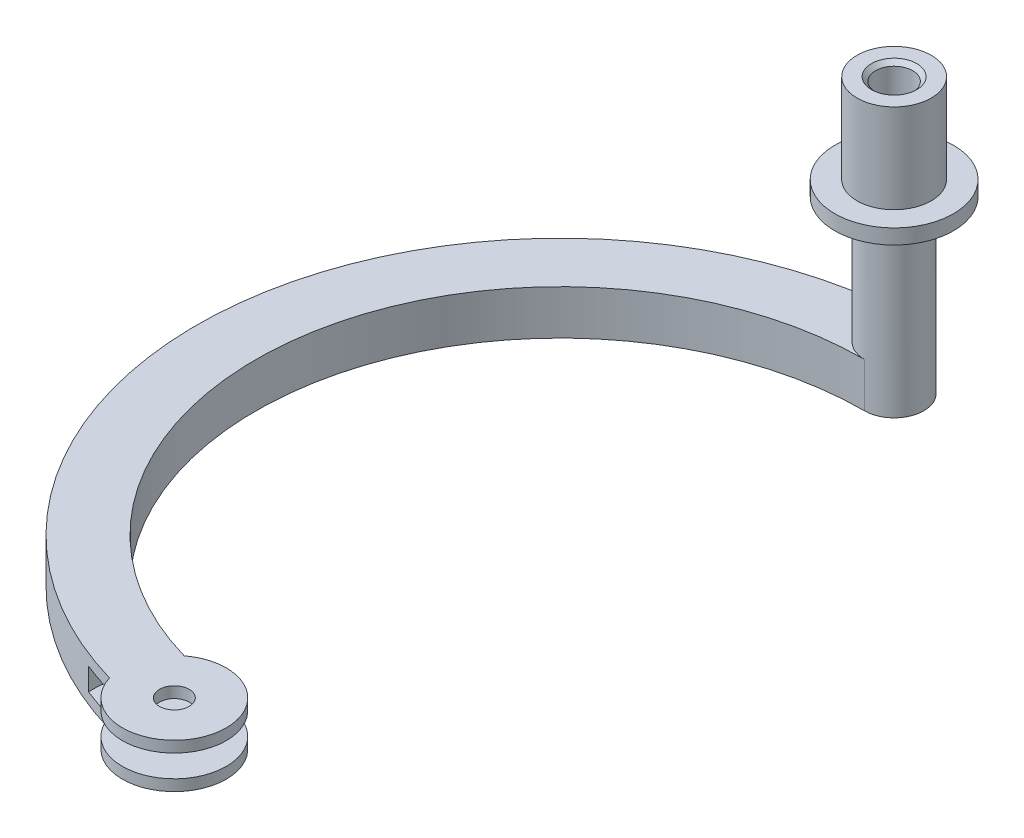
SolidWorks part; units mm, degrees
ref_plane "Front Plane" through (0, 0, 0) normal (0, 0, 1) x (1, 0, 0)
ref_plane "Top Plane" through (0, 0, 0) normal (0, 1, 0) x (1, 0, 0)
ref_plane "Right Plane" through (0, 0, 0) normal (1, 0, 0) x (0, 0, -1)
sketch "Sketch1" plane through (0, 0, 0) normal (0, 1, 0) x (1, 0, 0)
  circle A0 centre (0, 0) radius 2.5
  dimension "D1" = 5
extrude "Boss-Extrude1" add sketch "Sketch1" along normal blind 6
sketch "Sketch2" plane through (0, 0, 0) normal (0, -1, 0) x (1, 0, 0)
  circle A0 centre (0, 0) radius 4
  dimension "D1" = 8
extrude "Boss-Extrude2" add sketch "Sketch2" along normal blind 1
ref_plane "Plane1" through (0, -11, 0) normal (0, -1, 0) x (-1, 0, 0)
sketch "Sketch6" plane through (0, -11, 0) normal (0, -1, 0) x (-1, 0, 0)
  line L10 (0, 0) -> (0, -16.7806) construction
  arc A1 (6.8469, -46.0238) -> (5.6195, -42.2147) centre (3.5, -45) cw
  arc A2 (0, -2) -> (0, 2) centre (0, 0) cw
  arc A5 (0, 2) -> (6.8469, -46.0238) centre (0, -22.5) cw
  arc A6 (0, -2) -> (5.6195, -42.2147) centre (0, -22.5) cw
  dimension "D1" = 3.5
  dimension "D2" = 2
  dimension "D4" = 45
  dimension "D3" = 22.5
extrude "Boss-Extrude3" add sketch "Sketch6" along normal mid plane 3 separate body
sketch "Sketch7" plane through (0, -1, 0) normal (0, -1, 0) x (1, 0, 0)
  circle A3 centre (0, 0) radius 2
  arc A4 (0, -2) -> (0, 2) centre (0, 0) ccw construction
extrude "Boss-Extrude4" add sketch "Sketch7" along normal up to surface (8.5 mm away) contours A3 up to face at (-10.6815, -9.5, 21.1946)
ref_plane "Plane2" through (0, -11, 0) normal (0, 1, 0) x (1, 0, 0)
sketch "Sketch8" plane through (0, -11, 0) normal (0, 1, 0) x (1, 0, 0)
  circle A0 centre (-3.5, -45) radius 5.5
  arc A1 (-6.8469, -46.0238) -> (-5.6195, -42.2147) centre (-3.5, -45) ccw construction
  dimension "D1" = 2
extrude "Cut-Extrude1" cut sketch "Sketch8" against normal mid plane 1.5
sketch "Sketch9" plane through (0, -9.5, 0) normal (0, 1, 0) x (1, 0, 0)
  circle A0 centre (-3.5, -45) radius 1
  arc A1 (-6.8469, -46.0238) -> (-5.6195, -42.2147) centre (-3.5, -45) ccw construction
  dimension "D1" = 2
extrude "Cut-Extrude2" cut sketch "Sketch9" against normal through all
sketch "Sketch10" plane through (0, 6, 0) normal (0, 1, 0) x (1, 0, 0)
  circle A0 centre (0, 0) radius 2.5 construction
  point P0 (0, 0)
hole_wizard "M3 Tapped Hole2" positions "3DSketch4" profile "Sketch12" tap size "M3" standard "ISO"
sketch3d "3DSketch4"
  point P0 (0, 6, 0)
sketch "Sketch12" plane through (0, 6, 0) normal (1, 0, 0) x (0, 0, 1)
  line L0 (0, 0) -> (0, 8.2511)
  line L1 (0, 8.2511) -> (1.25, 7.5)
  line L2 (1.25, 7.5) -> (1.25, 0.275)
  line L3 (1.25, 0.275) -> (1.525, 0)
  line L5 (1.525, 0) -> (0, 0)
  line L6 (-1.25, 0.275) -> (-1.525, 0) construction
  line L10 (0, 8.2511) -> (-1.25, 7.5) construction
  line L11 (0, -6.35) -> (0, 107.95) construction
  dimension "Tap Drill Dia." = 2.5
  dimension "Tap Drill Depth" = 7.5
  dimension "Near C'Sink Dia." = 3.05
  dimension "Near C'Sink Angle" = 90
  dimension "Drill Angle" = 118
cosmetic thread "Hole Thread2" parameters "D1"=6, "D2"=3
cosmetic thread "Cosmetic Thread1" parameters "D1"=6, "D2"=3
